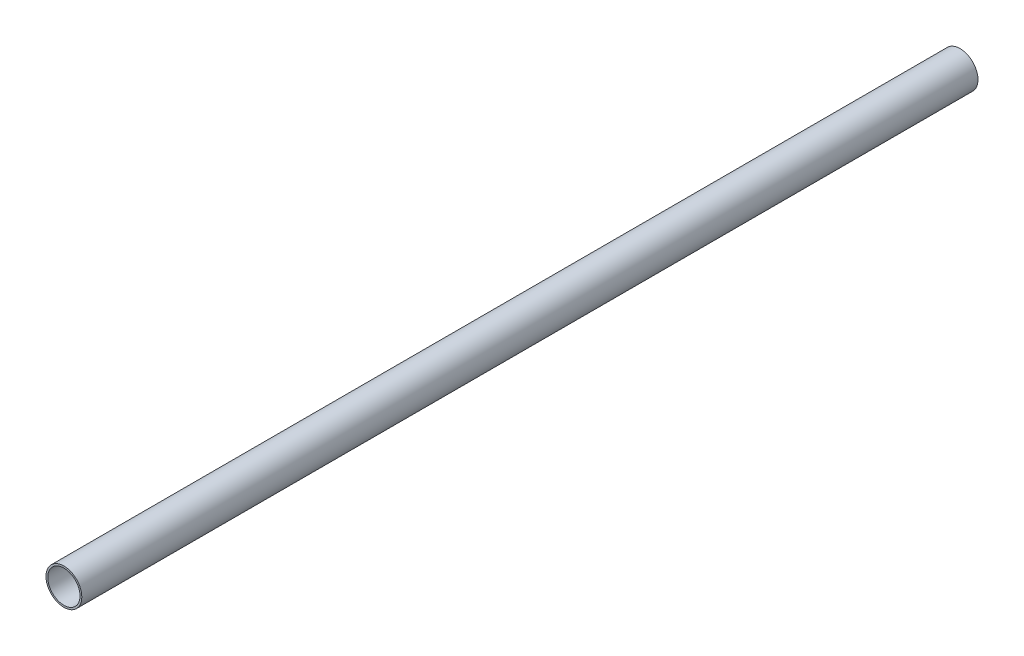
SolidWorks part; units mm, degrees
material "Carbon Fiber Tube - UD Approx"
ref_plane "Front Plane" through (0, 0, 0) normal (0, 0, 1) x (1, 0, 0)
ref_plane "Top Plane" through (0, 0, 0) normal (0, 1, 0) x (1, 0, 0)
ref_plane "Right Plane" through (0, 0, 0) normal (1, 0, 0) x (0, 0, -1)
sketch "Sketch1" plane through (0, 0, 0) normal (0, 0, 1) x (1, 0, 0)
  circle A0 centre (0, 0) radius 10
  circle A1 centre (0, 0) radius 9
  dimension "D1" = 20
  dimension "D2" = 18
extrude "Boss-Extrude1" add sketch "Sketch1" along normal blind 500
